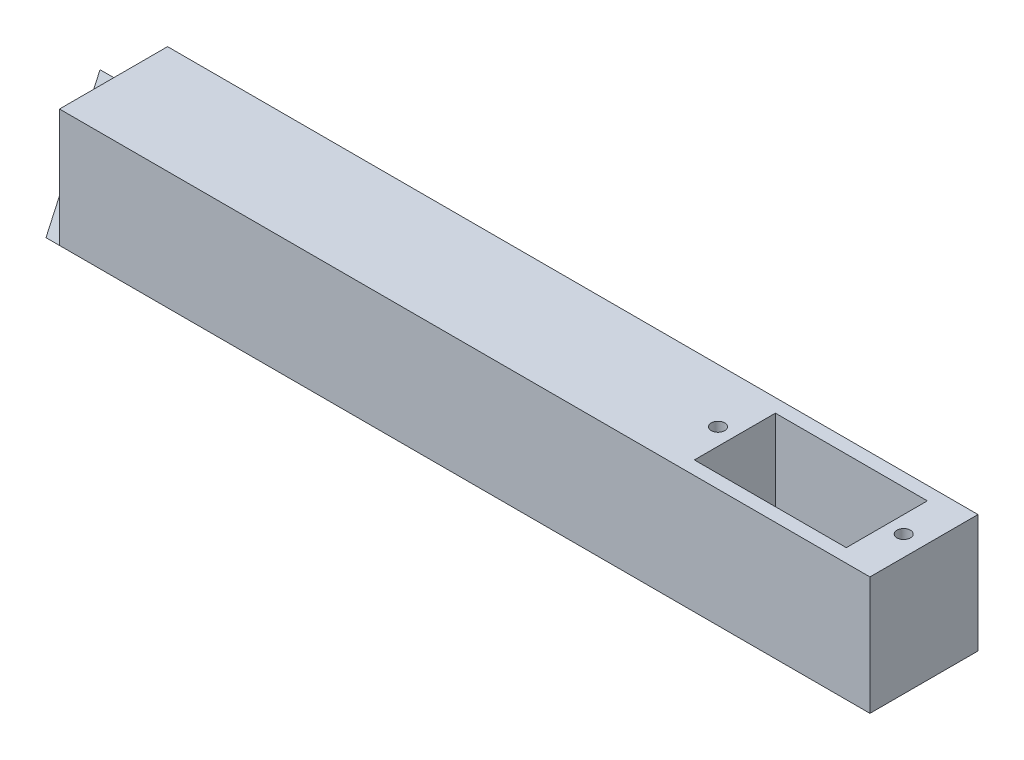
SolidWorks part; units mm, degrees
ref_plane "Ebene vorne" through (0, 0, 0) normal (0, 0, 1) x (1, 0, 0)
ref_plane "Ebene oben" through (0, 0, 0) normal (0, 1, 0) x (1, 0, 0)
ref_plane "Ebene rechts" through (0, 0, 0) normal (1, 0, 0) x (0, 0, -1)
sketch "Skizze1" plane through (0, 0, 0) normal (0, 1, 0) x (1, 0, 0)
  line L1 (-79.9317, -8) -> (40.0683, -8)
  line L2 (-79.9317, -8) -> (-79.9317, 8)
  line L3 (-79.9317, 8) -> (40.0683, 8)
  line L5 (40.0683, -8) -> (40.0683, 8)
  line L6 (-55, 0) -> (55, 0) construction
  line L12 (12.0683, -6) -> (34.5683, -6)
  line L13 (12.0683, -6) -> (12.0683, 6)
  line L15 (12.0683, 6) -> (34.5683, 6)
  line L16 (34.5683, -6) -> (34.5683, 6)
  line L17 (12.0683, -6) -> (34.5683, 6) construction
  line L18 (12.0683, 6) -> (34.5683, -6) construction
  point P0 (0, 0)
  point P6 (23.3183, 0)
  dimension "D1" = 120
  dimension "D2" = 22.5
  dimension "D3" = 12
  dimension "D4" = 16
  dimension "D5" = 92
extrude "Aufsatz-Linear austragen1" add sketch "Skizze1" along normal blind 17.5
sketch "Skizze3" plane through (-79.9317, 0, 0) normal (-1, 0, 0) x (0, 0, 1)
  line L0 (0, 0) -> (0, 17.5412) construction
  line L1 (0, 17.5412) -> (0, 8.7706) construction
  line L2 (-8, 8.7706) -> (8, 8.7706) construction
  line L3 (8, 8.7706) -> (0, 0) construction
  line L4 (0, 17.5412) -> (-8, 0)
  line L5 (-8, 0) -> (8, 0)
  line L6 (8, 0) -> (0, 17.5412)
extrude "Aufsatz-Linear austragen4" add sketch "Skizze3" along normal blind 2
sketch "Skizze4" plane through (0, 17.5, 0) normal (0, 1, 0) x (1, 0, 0)
  circle A0 centre (37.0683, 0) radius 1
  circle A1 centre (9.5683, 0) radius 1
  dimension "D1" = 2
  dimension "D2" = 2
extrude "Schnitt-Linear austragen1" cut sketch "Skizze4" against normal through all
sketch "Skizze6" plane through (-81.9317, 0, 0) normal (-1, 0, 0) x (0, 0, 1)
  circle A0 centre (0.05, 5.0878) radius 1
  dimension "D1" = 2
extrude "Schnitt-Linear austragen2" cut sketch "Skizze6" against normal blind 14
